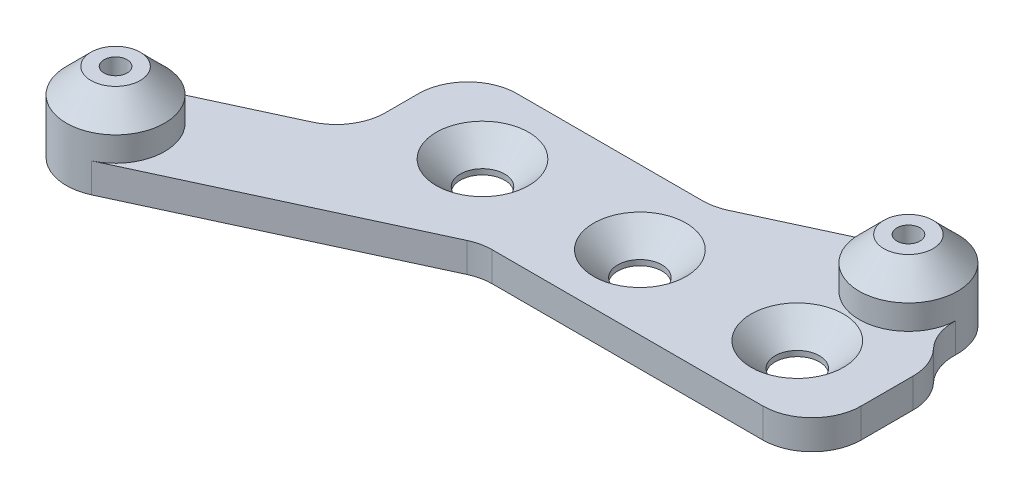
SolidWorks part; units mm, degrees
ref_plane "Front Plane" through (0, 0, 0) normal (0, 0, 1) x (1, 0, 0)
ref_plane "Top Plane" through (0, 0, 0) normal (0, 1, 0) x (1, 0, 0)
ref_plane "Right Plane" through (0, 0, 0) normal (1, 0, 0) x (0, 0, -1)
sketch "Sketch2" plane through (0, 0, 0) normal (0, 1, 0) x (1, 0, 0)
  line L0 (-35.7, -20.0376) -> (19.4, 5.4624)
  line L1 (-39.9, -10.9624) -> (15.2, 14.5376)
  arc A0 (-39.9, -10.9624) -> (-35.7, -20.0376) centre (-37.8, -15.5) ccw
  arc A1 (19.4, 5.4624) -> (15.2, 14.5376) centre (17.3, 10) ccw
  dimension "D1" = 5
extrude "Boss-Extrude2" add sketch "Sketch2" along normal blind 3
sketch "Sketch4" plane through (0, 0, 0) normal (0, 1, 0) x (1, 0, 0)
  line L1 (25, 7.5) -> (-25, 7.5)
  line L2 (25, 7.5) -> (25, -7.5)
  line L3 (25, -7.5) -> (-25, -7.5)
  line L4 (-25, 7.5) -> (-25, -7.5)
  line L5 (25, 7.5) -> (-25, -7.5) construction
  line L6 (25, -7.5) -> (-25, 7.5) construction
  point P0 (0, 0)
  dimension "D1" = 50
  dimension "D2" = 15
extrude "Boss-Extrude3" add sketch "Sketch4" along normal up to surface (3 mm away) up to face at (-10.25, 3, 2.75)
sketch "Sketch6" plane through (0, 3, 0) normal (0, 1, 0) x (1, 0, 0)
  circle A0 centre (-37.8, -15.5) radius 5
  circle A1 centre (17.3, 10) radius 5
  arc A2 (21.6301, 7.5) -> (15.2, 14.5376) centre (17.3, 10) ccw construction
  arc A3 (-39.9, -10.9624) -> (-35.7, -20.0376) centre (-37.8, -15.5) ccw construction
extrude "Boss-Extrude4" add sketch "Sketch6" along normal blind 5
fillet "Fillet1" radius 5 6 edges at (25, 1.5, -7.5) (-25, 1.5, 4.0667) (-25, 1.5, -7.5) (-0.0068, 1.5, -7.5) (-8.6089, 1.5, 7.5) (25, 1.5, 7.5)
fillet "Fillet2" radius 5 1 edges at (21.6301, 1.5, -7.5)
hole_wizard "CSK for M4 Countersunk Flat Head Screw1" positions "Sketch8" profile "Sketch7" countersink size "M4" standard "ISO" end condition through all
sketch "Sketch8" plane through (0, 3, 0) normal (0, 1, 0) x (1, 0, 0)
  line L0 (0, 0) -> (-50000, 0) construction
  line L1 (0, 0) -> (0, -50000) construction
  point P0 (0, 0)
  point P2 (-16, 0)
  point P4 (16, 0)
  dimension "D1" = 32
sketch "Sketch7" plane through (0, 3, 0) normal (1, 0, 0) x (0, 0, 1)
  line L0 (0, 0) -> (0, 3)
  line L1 (0, 3) -> (2.25, 3)
  line L2 (2.25, 3) -> (2.25, 2.45)
  line L3 (2.25, 2.45) -> (4.7, 0)
  line L5 (4.7, 0) -> (0, 0)
  line L6 (-2.25, 2.45) -> (-4.7, 0) construction
  line L11 (0, -6.35) -> (0, 107.95) construction
  dimension "Thru Hole Dia." = 4.5
  dimension "Thru Hole Depth" = 3
  dimension "Near C'Sink Dia." = 9.4
  dimension "Near C'Sink Angle" = 90
sketch "Sketch9" plane through (0, 8, 0) normal (0, 1, 0) x (1, 0, 0)
  circle A0 centre (-37.8, -15.5) radius 1.175
  circle A1 centre (17.3, 10) radius 1.175
  dimension "D1" = 2.35
extrude "Cut-Extrude2" cut sketch "Sketch9" against normal through all
chamfer "Chamfer1" distance 2.5 angle 45 2 edges at (17.3, 8, -5) (-37.8, 8, 20.5)
